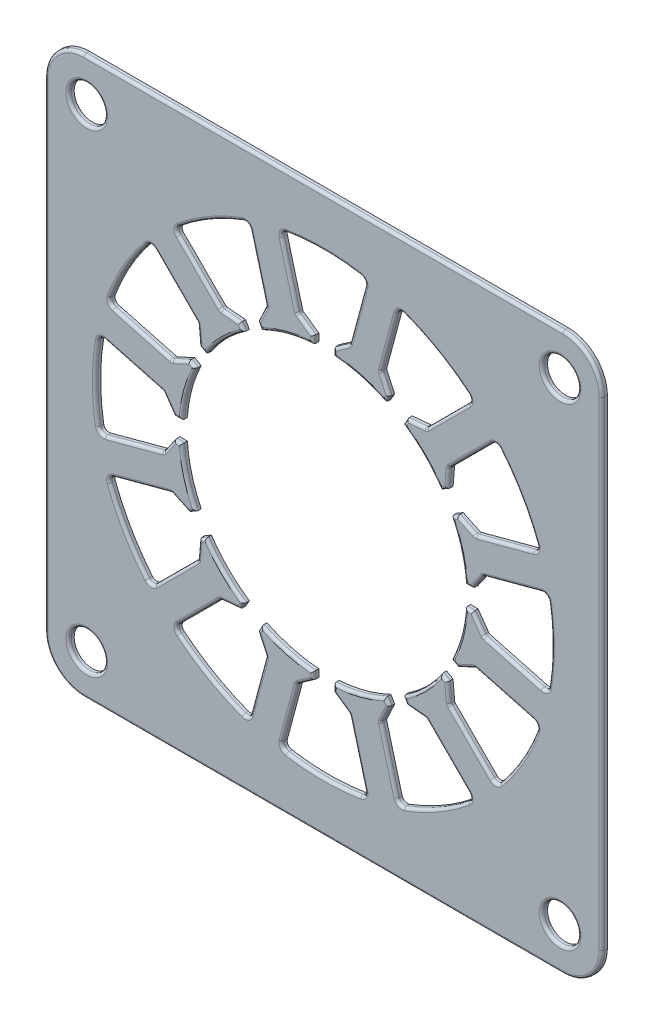
SolidWorks part; units mm, degrees
ref_plane "Front" through (0, 0, 0) normal (0, 0, 1) x (1, 0, 0)
ref_plane "Top" through (0, 0, 0) normal (0, 1, 0) x (1, 0, 0)
ref_plane "Right" through (0, 0, 0) normal (1, 0, 0) x (0, 0, -1)
sketch "Sketch1" plane through (0, 0, 0) normal (0, 0, 1) x (1, 0, 0)
  line L1 (-50, 50) -> (50, 50)
  line L2 (-50, 50) -> (-50, -50)
  line L3 (-50, -50) -> (50, -50)
  line L4 (50, 50) -> (50, -50)
  circle A0 centre (0, 0) radius 50 construction
  circle A1 centre (0, 0) radius 25.5
  dimension "D1" = 100
  dimension "D2" = 51
extrude "Lamination Extruction" add sketch "Sketch1" along normal blind 1
ref_axis "Axis1" through (0, 0, 1) along (0, 0, -1)
sketch "Sketch2" plane through (0, 0, 1) normal (0, 0, 1) x (1, 0, 0)
  line L0 (0, 0) -> (0, 50) construction
  line L1 (50, 50) -> (-50, 50) construction
  line L2 (-1.825, 26.7846) -> (1.825, 26.7846) construction
  line L3 (7.75, 40.2609) -> (4.6735, 28.7791)
  line L4 (4.6735, 28.7791) -> (1.825, 26.7846)
  line L5 (-1.825, 26.7846) -> (-1.825, 25.4346)
  line L6 (-7.75, 40.2609) -> (-4.6735, 28.7791)
  line L7 (-4.6735, 28.7791) -> (-1.825, 26.7846)
  line L8 (1.825, 26.7846) -> (1.825, 25.4346)
  line L9 (-4.6735, 28.7791) -> (4.6735, 28.7791) construction
  arc A1 (-7.75, 40.2609) -> (7.75, 40.2609) centre (0, 0) cw
  circle A3 centre (0, 0) radius 25.5 construction
  arc A4 (1.825, 25.4346) -> (-1.825, 25.4346) centre (0, 0) ccw
  point P7 (0, 26.7846)
  point P16 (0, 41)
  point P19 (0, 28.7791)
  circle M15 centre (0, 0) radius 25.5
  dimension "D2" = 41
  dimension "D1" = 30
  dimension "D3" = 15.5
  dimension "D6" = 35
  dimension "D4" = 1.35
  dimension "D5" = 3.65
extrude "Slot Cut" cut sketch "Sketch2" against normal through all contours A1 L6 L7 L5 L8 L4 L3 M15 region at (0, 34.4506, 1)
fillet "Slot Fillet Top" radius 1 2 edges at (7.75, 40.2609, 0.5) (-7.75, 40.2609, 0.5)
fillet "Slot Fillet Bottom" radius 0.5 2 edges at (4.6735, 28.7791, 0.5) (-4.6735, 28.7791, 0.5)
pattern_circular "Slot Duplicate" count 12 over 360 about axis through (0, 0, 1) along (0, 0, -1) of "Slot Cut", "Slot Fillet Top", "Slot Fillet Bottom"
sketch "Sketch3" plane through (0, 0, 1) normal (0, 0, 1) x (1, 0, 0)
  line L1 (42.5, 42.5) -> (-42.5, 42.5) construction
  line L2 (42.5, 42.5) -> (42.5, -42.5) construction
  line L3 (42.5, -42.5) -> (-42.5, -42.5) construction
  line L4 (-42.5, 42.5) -> (-42.5, -42.5) construction
  line L5 (42.5, 42.5) -> (-42.5, -42.5) construction
  line L6 (42.5, -42.5) -> (-42.5, 42.5) construction
  circle A1 centre (-42.5, 42.5) radius 3.25
  circle A2 centre (42.5, 42.5) radius 3.25
  circle A3 centre (42.5, -42.5) radius 3.25
  circle A4 centre (-42.5, -42.5) radius 3.25
  point P0 (0, 0)
  dimension "D2" = 6.5
  dimension "D1" = 85
extrude "Bolt Hole Cut" cut sketch "Sketch3" against normal through all
fillet "Corner Fillet" radius 7 4 edges at (-50, 50, 0.5) (-50, -50, 0.5) (50, -50, 0.5) (50, 50, 0.5)
fillet "Fillet1" radius 0.5 156 edges at (38.321, 13.6461, 1) (35.507, 20.5, 1) (30.9784, 26.3639, 1) (26.4687, 22.3189, 1) (22.6158, 18.4234, 1) (22.4273, 16.6142, 1) (18.0312, 18.0312, 1) (16.6142, 22.4273, 1) (18.4234, 22.6158, 1) (22.3189, 26.4687, 1) (26.3639, 30.9784, 1) (20.5, 35.507, 1) (13.6461, 38.321, 1) (11.7631, 32.5631, 1) (10.3742, 27.263, 1) (11.1155, 25.602, 1) (6.5999, 24.6311, 1) (3.1747, 27.7297, 1) (4.6472, 28.7975, 1) (6.0944, 34.082, 1) (7.3426, 40.01, 1) (0, 41, 1) (-7.3426, 40.01, 1) (-6.0944, 34.082, 1) (-4.6472, 28.7975, 1) (-3.1747, 27.7297, 1) (-6.5999, 24.6311, 1) (-11.1155, 25.602, 1) (-10.3742, 27.263, 1) (-11.7631, 32.5631, 1) (-13.6461, 38.321, 1) (-20.5, 35.507, 1) (-26.3639, 30.9784, 1) (-22.3189, 26.4687, 1) (-18.4234, 22.6158, 1) (-16.6142, 22.4273, 1) (-18.0312, 18.0312, 1) (-22.4273, 16.6142, 1) (-22.6158, 18.4234, 1) (-26.4687, 22.3189, 1) (-30.9784, 26.3639, 1) (-35.507, 20.5, 1) (-38.321, 13.6461, 1) (-32.5631, 11.7631, 1) (-27.263, 10.3742, 1) (-25.602, 11.1155, 1) (-24.6311, 6.5999, 1) (-27.7297, 3.1747, 1) (-28.7975, 4.6472, 1) (-34.082, 6.0944, 1) (-40.01, 7.3426, 1) (-41, 0, 1) (-40.01, -7.3426, 1) (-34.082, -6.0944, 1) (-28.7975, -4.6472, 1) (-27.7297, -3.1747, 1) (-24.6311, -6.5999, 1) (-25.602, -11.1155, 1) (-27.263, -10.3742, 1) (-32.5631, -11.7631, 1) (-38.321, -13.6461, 1) (-35.507, -20.5, 1) (-30.9784, -26.3639, 1) (-26.4687, -22.3189, 1) (-22.6158, -18.4234, 1) (-22.4273, -16.6142, 1) (-18.0312, -18.0312, 1) (-16.6142, -22.4273, 1) (-18.4234, -22.6158, 1) (-22.3189, -26.4687, 1) (-26.3639, -30.9784, 1) (-20.5, -35.507, 1) (-13.6461, -38.321, 1) (-11.7631, -32.5631, 1) (-10.3742, -27.263, 1) (-11.1155, -25.602, 1) (-6.5999, -24.6311, 1) (-3.1747, -27.7297, 1) (-4.6472, -28.7975, 1) (-6.0944, -34.082, 1) (-7.3426, -40.01, 1) (0, -41, 1) (7.3426, -40.01, 1) (6.0944, -34.082, 1) (4.6472, -28.7975, 1) (3.1747, -27.7297, 1) (6.5999, -24.6311, 1) (11.1155, -25.602, 1) (10.3742, -27.263, 1) (11.7631, -32.5631, 1) (13.6461, -38.321, 1) (20.5, -35.507, 1) (26.3639, -30.9784, 1) (22.3189, -26.4687, 1) (18.4234, -22.6158, 1) (16.6142, -22.4273, 1) (18.0312, -18.0312, 1) (22.4273, -16.6142, 1) (22.6158, -18.4234, 1) (26.4687, -22.3189, 1) (30.9784, -26.3639, 1) (35.507, -20.5, 1) (38.321, -13.6461, 1) (32.5631, -11.7631, 1) (27.263, -10.3742, 1) (25.602, -11.1155, 1) (24.6311, -6.5999, 1) (27.7297, -3.1747, 1) (28.7975, -4.6472, 1) (34.082, -6.0944, 1) (40.01, -7.3426, 1) (41, 0, 1) (40.01, 7.3426, 1) (34.082, 6.0944, 1) (28.7975, 4.6472, 1) (27.7297, 3.1747, 1) (24.6311, 6.5999, 1) (25.602, 11.1155, 1) (27.263, 10.3742, 1) (32.5631, 11.7631, 1) (47.9497, 47.9497, 1) (50, 0, 1) (47.9497, -47.9497, 1) (0, -50, 1) (-47.9497, -47.9497, 1) (-50, 0, 1) (-47.9497, 47.9497, 1) (0, 50, 1) (45.75, 42.5, 1) (-39.25, -42.5, 1) (45.75, -42.5, 1) (-39.25, 42.5, 1) (21.6991, 14.6353, 1) (14.6353, 21.6991, 1) (11.4743, 23.5241, 1) (1.825, 26.1096, 1) (-1.825, 26.1096, 1) (-11.4743, 23.5241, 1) (-14.6353, 21.6991, 1) (-21.6991, 14.6353, 1) (-23.5241, 11.4743, 1) (-26.1096, 1.825, 1) (-26.1096, -1.825, 1) (-23.5241, -11.4743, 1) (-21.6991, -14.6353, 1) (-14.6353, -21.6991, 1) (-11.4743, -23.5241, 1) (-1.825, -26.1096, 1) (1.825, -26.1096, 1) (11.4743, -23.5241, 1) (14.6353, -21.6991, 1) (21.6991, -14.6353, 1) (23.5241, -11.4743, 1) (26.1096, -1.825, 1) (26.1096, 1.825, 1) (23.5241, 11.4743, 1)
equation "\"DS1\"= 100mm"
equation "\"D1@Sketch1\"=\"DS1\""
equation "\"DS2\"=51"
equation "\"D2@Sketch1\"=\"DS2\""
equation "\"HEIGHT\"=1"
equation "\"D1@Lamination Extruction\" = \"HEIGHT\""
equation "\"AngSlot\"=30"
equation "\"D1@Sketch2\"=\"AngSlot\""
equation "\"DSS\"= 15.5mm"
equation "\"D2@Sketch2\"=\"DSS\"+\"DS2\"/2"
equation "\"WSSB\"=15.5"
equation "\"D3@Sketch2\"=\"WSSB\""
equation "\"WSSO\"=3.65"
equation "\"HSTT\"=1.35"
equation "\"AngSTT\"=35"
equation "\"D6@Sketch2\"=\"AngSTT\""
equation "\"D4@Sketch2\"=\"HSTT\""
equation "\"D5@Sketch2\"=\"WSSO\""
equation "\"FRSSB\"=1"
equation "\"D1@Slot Fillet Top\" = \"FRSSB\""
equation "\"FRSST\"=0.5"
equation "\"D1@Slot Fillet Bottom\" = \"FRSST\""
equation "\"SLOTS\"=12"
equation "\"D1@Slot Duplicate\" = \"SLOTS\""
equation "\"HOLE_BOLT\"= 85"
equation "\"D1@Sketch3\"=\"HOLE_BOLT\""
equation "\"BOLT_DIA\"=6.5"
equation "\"D2@Sketch3\"=\"BOLT_DIA\""
equation "\"LAM_FILLET\"=7"
equation "\"D1@Corner Fillet\"=\"LAM_FILLET\""
